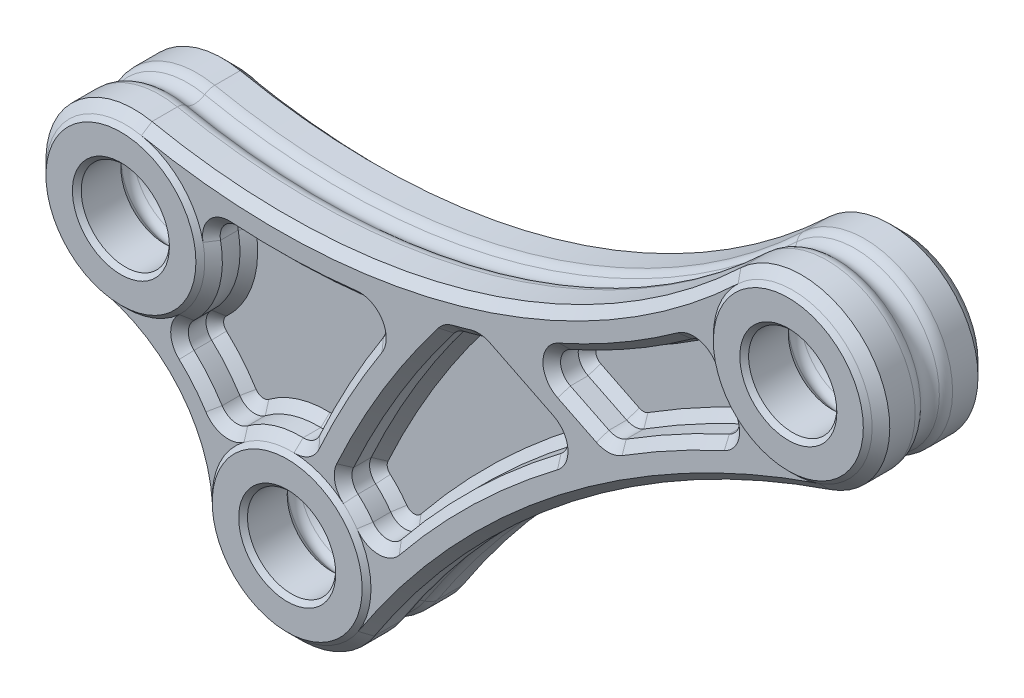
SolidWorks part; units mm, degrees
material "7075-T6，板材(SS)"
ref_plane "前视基准面" through (0, 0, 0) normal (0, 0, 1) x (1, 0, 0)
ref_plane "上视基准面" through (0, 0, 0) normal (0, 1, 0) x (1, 0, 0)
ref_plane "右视基准面" through (0, 0, 0) normal (1, 0, 0) x (0, 0, -1)
sketch "Sketch1" plane through (0, 0, 0) normal (0, 0, 1) x (1, 0, 0)
  line L0 (122.9511, -18.8201) -> (93.1268, -73.5554)
  line L1 (93.1268, -73.5554) -> (122.7846, -133.2618)
  line L2 (122.7846, -133.2618) -> (122.9511, -18.8201)
  line L3 (0, 0) -> (71.4018, 54.7885)
  line L4 (71.4018, 54.7885) -> (-333.3333, 54.7885)
  line L5 (-333.3333, 54.7885) -> (0, 0)
  line L6 (0, 0) -> (-333.3333, 54.7885)
  line L7 (-333.3333, 54.7885) -> (-333.3333, 0)
  line L8 (-333.3333, 0) -> (0, 0)
  line L9 (71.4018, 54.7885) -> (122.9511, -18.8201)
  line L10 (122.9511, -18.8201) -> (94.2741, 2.9429)
  line L11 (94.2741, 2.9429) -> (71.4018, 54.7885)
  line L12 (71.4018, 54.7885) -> (94.2741, 2.9429)
  line L13 (94.2741, 2.9429) -> (71.4018, 54.7885)
  line L14 (94.2741, 2.9429) -> (18.6205, -18.6205)
  line L15 (18.6205, -18.6205) -> (37.467, -41.2946)
  line L16 (37.467, -41.2946) -> (94.2741, 2.9429)
  line L17 (94.2741, 2.9429) -> (37.467, -41.2946)
  line L18 (37.467, -41.2946) -> (94.2741, 2.9429)
  line L19 (184.818, -172.2512) -> (184.6311, -172.3314)
  line L20 (184.6311, -172.3314) -> (184.444, -172.4113)
  line L21 (184.444, -172.4113) -> (184.2569, -172.4911)
  line L22 (184.2569, -172.4911) -> (184.0696, -172.5706)
  line L23 (184.0696, -172.5706) -> (183.8823, -172.6498)
  line L24 (183.8823, -172.6498) -> (183.6948, -172.7288)
  line L25 (183.6948, -172.7288) -> (183.5072, -172.8076)
  line L26 (183.5072, -172.8076) -> (183.3195, -172.8862)
  line L27 (183.3195, -172.8862) -> (183.1318, -172.9645)
  line L28 (183.1318, -172.9645) -> (182.9439, -173.0426)
  line L29 (182.9439, -173.0426) -> (182.7559, -173.1204)
  line L30 (182.7559, -173.1204) -> (182.5679, -173.198)
  line L31 (182.5679, -173.198) -> (182.3797, -173.2753)
  line L32 (182.3797, -173.2753) -> (182.1914, -173.3524)
  line L33 (182.1914, -173.3524) -> (182.003, -173.4293)
  line L34 (182.003, -173.4293) -> (181.8146, -173.5059)
  line L35 (181.8146, -173.5059) -> (181.626, -173.5823)
  line L36 (181.626, -173.5823) -> (181.4374, -173.6584)
  line L37 (181.4374, -173.6584) -> (181.2486, -173.7343)
  line L38 (181.2486, -173.7343) -> (181.0598, -173.8099)
  line L39 (181.0598, -173.8099) -> (180.8709, -173.8853)
  line L40 (180.8709, -173.8853) -> (180.6819, -173.9604)
  line L41 (180.6819, -173.9604) -> (180.4928, -174.0353)
  line L42 (180.4928, -174.0353) -> (180.3036, -174.11)
  line L43 (180.3036, -174.11) -> (180.1143, -174.1843)
  line L44 (180.1143, -174.1843) -> (179.9249, -174.2585)
  line L45 (179.9249, -174.2585) -> (179.7355, -174.3324)
  line L46 (179.7355, -174.3324) -> (179.546, -174.406)
  line L47 (179.546, -174.406) -> (179.3564, -174.4794)
  line L48 (179.3564, -174.4794) -> (179.1667, -174.5525)
  line L49 (179.1667, -174.5525) -> (178.9769, -174.6254)
  line L50 (178.9769, -174.6254) -> (178.7871, -174.698)
  line L51 (178.7871, -174.698) -> (178.5972, -174.7704)
  line L52 (178.5972, -174.7704) -> (178.4072, -174.8425)
  line L53 (178.4072, -174.8425) -> (178.2172, -174.9143)
  line L54 (178.2172, -174.9143) -> (178.027, -174.9859)
  line L55 (178.027, -174.9859) -> (177.8368, -175.0573)
  line L56 (177.8368, -175.0573) -> (177.6466, -175.1283)
  line L57 (177.6466, -175.1283) -> (177.4563, -175.1992)
  line L58 (177.4563, -175.1992) -> (177.2659, -175.2697)
  line L59 (177.2659, -175.2697) -> (177.0754, -175.34)
  line L60 (177.0754, -175.34) -> (176.8849, -175.41)
  line L61 (176.8849, -175.41) -> (176.6943, -175.4798)
  line L62 (176.6943, -175.4798) -> (176.5037, -175.5493)
  line L63 (176.5037, -175.5493) -> (176.313, -175.6186)
  line L64 (176.313, -175.6186) -> (176.1223, -175.6875)
  line L65 (176.1223, -175.6875) -> (175.9315, -175.7562)
  line L66 (175.9315, -175.7562) -> (175.7407, -175.8247)
  line L67 (175.7407, -175.8247) -> (175.5498, -175.8928)
  line L68 (175.5498, -175.8928) -> (175.3588, -175.9608)
  line L69 (175.3588, -175.9608) -> (175.1679, -176.0284)
  line L70 (175.1679, -176.0284) -> (174.9768, -176.0958)
  line L71 (174.9768, -176.0958) -> (174.7858, -176.1629)
  line L72 (174.7858, -176.1629) -> (174.5947, -176.2297)
  line L73 (174.5947, -176.2297) -> (174.4036, -176.2962)
  line L74 (174.4036, -176.2962) -> (174.2124, -176.3625)
  line L75 (174.2124, -176.3625) -> (174.0212, -176.4285)
  line L76 (174.0212, -176.4285) -> (173.8299, -176.4943)
  line L77 (173.8299, -176.4943) -> (173.6387, -176.5597)
  line L78 (173.6387, -176.5597) -> (173.4474, -176.6249)
  line L79 (173.4474, -176.6249) -> (173.2561, -176.6898)
  line L80 (173.2561, -176.6898) -> (173.0648, -176.7545)
  line L81 (173.0648, -176.7545) -> (172.8734, -176.8188)
  line L82 (172.8734, -176.8188) -> (172.682, -176.8829)
  line L83 (172.682, -176.8829) -> (172.4906, -176.9467)
  line L84 (172.4906, -176.9467) -> (172.2992, -177.0102)
  line L85 (172.2992, -177.0102) -> (172.1078, -177.0735)
  line L86 (172.1078, -177.0735) -> (171.9164, -177.1365)
  line L87 (171.9164, -177.1365) -> (171.725, -177.1991)
  line L88 (171.725, -177.1991) -> (171.5335, -177.2616)
  line L89 (171.5335, -177.2616) -> (171.3421, -177.3237)
  line L90 (171.3421, -177.3237) -> (171.1507, -177.3855)
  line L91 (171.1507, -177.3855) -> (170.9592, -177.4471)
  line L92 (170.9592, -177.4471) -> (170.7678, -177.5083)
  line L93 (170.7678, -177.5083) -> (170.5764, -177.5693)
  line L94 (170.5764, -177.5693) -> (170.385, -177.63)
  line L95 (170.385, -177.63) -> (170.1936, -177.6905)
  line L96 (170.1936, -177.6905) -> (170.0022, -177.7506)
  line L97 (170.0022, -177.7506) -> (169.8108, -177.8104)
  line L98 (169.8108, -177.8104) -> (169.6194, -177.87)
  line L99 (169.6194, -177.87) -> (169.4281, -177.9293)
  line L100 (169.4281, -177.9293) -> (169.2368, -177.9883)
  line L101 (169.2368, -177.9883) -> (169.0455, -178.047)
  line L102 (169.0455, -178.047) -> (168.8543, -178.1054)
  line L103 (168.8543, -178.1054) -> (168.6631, -178.1635)
  line L104 (168.6631, -178.1635) -> (168.4719, -178.2213)
  line L105 (168.4719, -178.2213) -> (168.2807, -178.2789)
  line L106 (168.2807, -178.2789) -> (168.0896, -178.3361)
  line L107 (168.0896, -178.3361) -> (167.8985, -178.3931)
  line L108 (167.8985, -178.3931) -> (167.7075, -178.4497)
  line L109 (167.7075, -178.4497) -> (167.5165, -178.5061)
  line L110 (167.5165, -178.5061) -> (167.3256, -178.5622)
  line L111 (167.3256, -178.5622) -> (167.1347, -178.618)
  line L112 (167.1347, -178.618) -> (166.9439, -178.6735)
  line L113 (166.9439, -178.6735) -> (166.7531, -178.7287)
  line L114 (166.7531, -178.7287) -> (166.5624, -178.7836)
  line L115 (166.5624, -178.7836) -> (166.3718, -178.8382)
  line L116 (166.3718, -178.8382) -> (166.1812, -178.8925)
  line L117 (166.1812, -178.8925) -> (165.9907, -178.9465)
  line L118 (165.9907, -178.9465) -> (165.8003, -179.0002)
  line L119 (165.8003, -179.0002) -> (165.6099, -179.0537)
  line L120 (165.6099, -179.0537) -> (165.4196, -179.1068)
  line L121 (165.4196, -179.1068) -> (165.2294, -179.1596)
  line L122 (165.2294, -179.1596) -> (165.0393, -179.2122)
  line L123 (165.0393, -179.2122) -> (164.8492, -179.2644)
  line L124 (164.8492, -179.2644) -> (164.6593, -179.3164)
  line L125 (164.6593, -179.3164) -> (164.4694, -179.368)
  line L126 (164.4694, -179.368) -> (164.2796, -179.4193)
  line L127 (164.2796, -179.4193) -> (164.09, -179.4704)
  line L128 (164.09, -179.4704) -> (163.9004, -179.5211)
  line L129 (163.9004, -179.5211) -> (163.7109, -179.5716)
  line L130 (163.7109, -179.5716) -> (163.5215, -179.6218)
  line L131 (163.5215, -179.6218) -> (163.3323, -179.6716)
  line L132 (163.3323, -179.6716) -> (163.1431, -179.7212)
  line L133 (163.1431, -179.7212) -> (162.9541, -179.7704)
  line L134 (162.9541, -179.7704) -> (162.7651, -179.8194)
  line L135 (162.7651, -179.8194) -> (162.5763, -179.868)
  line L136 (162.5763, -179.868) -> (162.3877, -179.9164)
  line L137 (162.3877, -179.9164) -> (162.1991, -179.9644)
  line L138 (162.1991, -179.9644) -> (162.0107, -180.0122)
  line L139 (162.0107, -180.0122) -> (161.8224, -180.0596)
  line L140 (161.8224, -180.0596) -> (161.6342, -180.1068)
  line L141 (161.6342, -180.1068) -> (161.4462, -180.1536)
  line L142 (161.4462, -180.1536) -> (161.2583, -180.2002)
  line L143 (161.2583, -180.2002) -> (161.0705, -180.2464)
  line L144 (161.0705, -180.2464) -> (160.8829, -180.2924)
  line L145 (160.8829, -180.2924) -> (160.6955, -180.338)
  line L146 (160.6955, -180.338) -> (160.5082, -180.3834)
  line L147 (160.5082, -180.3834) -> (160.321, -180.4284)
  line L148 (160.321, -180.4284) -> (160.134, -180.4732)
  line L149 (160.134, -180.4732) -> (159.9472, -180.5176)
  line L150 (159.9472, -180.5176) -> (159.7605, -180.5617)
  line L151 (159.7605, -180.5617) -> (159.574, -180.6056)
  line L152 (159.574, -180.6056) -> (159.3877, -180.6491)
  line L153 (159.3877, -180.6491) -> (159.2015, -180.6924)
  line L154 (159.2015, -180.6924) -> (159.0156, -180.7353)
  line L155 (159.0156, -180.7353) -> (158.8298, -180.7779)
  line L156 (158.8298, -180.7779) -> (158.6441, -180.8203)
  line L157 (158.6441, -180.8203) -> (158.4587, -180.8623)
  line L158 (158.4587, -180.8623) -> (158.2735, -180.904)
  line L159 (158.2735, -180.904) -> (158.0884, -180.9455)
  line L160 (158.0884, -180.9455) -> (157.9035, -180.9866)
  line L161 (157.9035, -180.9866) -> (157.7189, -181.0274)
  line L162 (157.7189, -181.0274) -> (157.5344, -181.068)
  line L163 (157.5344, -181.068) -> (157.3502, -181.1082)
  line L164 (157.3502, -181.1082) -> (157.1661, -181.1481)
  line L165 (157.1661, -181.1481) -> (156.9823, -181.1878)
  line L166 (156.9823, -181.1878) -> (156.7986, -181.2271)
  line L167 (156.7986, -181.2271) -> (156.6152, -181.2662)
  line L168 (156.6152, -181.2662) -> (156.432, -181.3049)
  line L169 (156.432, -181.3049) -> (156.249, -181.3433)
  line L170 (156.249, -181.3433) -> (156.0663, -181.3815)
  line L171 (156.0663, -181.3815) -> (155.8838, -181.4193)
  line L172 (155.8838, -181.4193) -> (155.7015, -181.4569)
  line L173 (155.7015, -181.4569) -> (155.5194, -181.4941)
  line L174 (155.5194, -181.4941) -> (155.3376, -181.5311)
  line L175 (155.3376, -181.5311) -> (155.156, -181.5678)
  line L176 (155.156, -181.5678) -> (154.9747, -181.6041)
  line L177 (154.9747, -181.6041) -> (154.7936, -181.6402)
  line L178 (154.7936, -181.6402) -> (154.6127, -181.676)
  line L179 (154.6127, -181.676) -> (154.4322, -181.7114)
  line L180 (154.4322, -181.7114) -> (154.2518, -181.7466)
  line L181 (154.2518, -181.7466) -> (154.0718, -181.7815)
  line L182 (154.0718, -181.7815) -> (153.892, -181.8161)
  line L183 (153.892, -181.8161) -> (153.7124, -181.8504)
  line L184 (153.7124, -181.8504) -> (153.5331, -181.8844)
  line L185 (153.5331, -181.8844) -> (153.3541, -181.9181)
  line L186 (153.3541, -181.9181) -> (153.1754, -181.9516)
  line L187 (153.1754, -181.9516) -> (152.9969, -181.9847)
  line L188 (152.9969, -181.9847) -> (152.8188, -182.0176)
  line L189 (152.8188, -182.0176) -> (152.6409, -182.0501)
  line L190 (152.6409, -182.0501) -> (152.4633, -182.0824)
  line L191 (152.4633, -182.0824) -> (152.286, -182.1144)
  line L192 (152.286, -182.1144) -> (152.109, -182.1461)
  line L193 (152.109, -182.1461) -> (151.9322, -182.1775)
  line L194 (151.9322, -182.1775) -> (151.7558, -182.2086)
  line L195 (151.7558, -182.2086) -> (151.5797, -182.2394)
  line L196 (151.5797, -182.2394) -> (151.4039, -182.27)
  line L197 (151.4039, -182.27) -> (151.2284, -182.3002)
  line L198 (151.2284, -182.3002) -> (151.0532, -182.3302)
  line L199 (151.0532, -182.3302) -> (150.8783, -182.3599)
  line L200 (150.8783, -182.3599) -> (150.7037, -182.3893)
  line L201 (150.7037, -182.3893) -> (150.5295, -182.4184)
  line L202 (150.5295, -182.4184) -> (150.3555, -182.4473)
  line L203 (150.3555, -182.4473) -> (150.1819, -182.4758)
  line L204 (150.1819, -182.4758) -> (150.0087, -182.5041)
  line L205 (150.0087, -182.5041) -> (149.8357, -182.5321)
  line L206 (149.8357, -182.5321) -> (149.6631, -182.5598)
  line L207 (149.6631, -182.5598) -> (149.4908, -182.5873)
  line L208 (149.4908, -182.5873) -> (149.3189, -182.6145)
  line L209 (149.3189, -182.6145) -> (149.1473, -182.6413)
  line L210 (149.1473, -182.6413) -> (148.9761, -182.668)
  line L211 (148.9761, -182.668) -> (148.8052, -182.6943)
  line L212 (148.8052, -182.6943) -> (148.6347, -182.7204)
  line L213 (148.6347, -182.7204) -> (148.4645, -182.7462)
  line L214 (148.4645, -182.7462) -> (148.2946, -182.7717)
  line L215 (148.2946, -182.7717) -> (148.1252, -182.797)
  line L216 (148.1252, -182.797) -> (147.9561, -182.8219)
  line L217 (147.9561, -182.8219) -> (147.7873, -182.8467)
  line L218 (147.7873, -182.8467) -> (147.619, -182.8711)
  line L219 (147.619, -182.8711) -> (147.451, -182.8953)
  line L220 (147.451, -182.8953) -> (147.2833, -182.9192)
  line L221 (147.2833, -182.9192) -> (147.1161, -182.9429)
  line L222 (147.1161, -182.9429) -> (146.9492, -182.9662)
  line L223 (146.9492, -182.9662) -> (146.7827, -182.9894)
  line L224 (146.7827, -182.9894) -> (146.6166, -183.0122)
  line L225 (146.6166, -183.0122) -> (146.4509, -183.0348)
  line L226 (146.4509, -183.0348) -> (146.2856, -183.0571)
  line L227 (146.2856, -183.0571) -> (146.1206, -183.0792)
  line L228 (146.1206, -183.0792) -> (145.9561, -183.101)
  line L229 (145.9561, -183.101) -> (145.7919, -183.1226)
  line L230 (145.7919, -183.1226) -> (145.6282, -183.1439)
  line L231 (145.6282, -183.1439) -> (145.4649, -183.165)
  line L232 (145.4649, -183.165) -> (145.3019, -183.1858)
  line L233 (145.3019, -183.1858) -> (145.1394, -183.2063)
  line L234 (145.1394, -183.2063) -> (144.9773, -183.2266)
  line L235 (144.9773, -183.2266) -> (144.8156, -183.2466)
  line L236 (144.8156, -183.2466) -> (144.6543, -183.2664)
  line L237 (144.6543, -183.2664) -> (144.4934, -183.286)
  line L238 (144.4934, -183.286) -> (144.3329, -183.3053)
  line L239 (144.3329, -183.3053) -> (144.1729, -183.3243)
  line L240 (144.1729, -183.3243) -> (144.0133, -183.3431)
  line L241 (144.0133, -183.3431) -> (143.8541, -183.3617)
  line L242 (143.8541, -183.3617) -> (143.6953, -183.38)
  line L243 (143.6953, -183.38) -> (143.537, -183.3981)
  line L244 (143.537, -183.3981) -> (143.3791, -183.4159)
  line L245 (143.3791, -183.4159) -> (143.2217, -183.4335)
  line L246 (143.2217, -183.4335) -> (143.0646, -183.4508)
  line L247 (143.0646, -183.4508) -> (142.908, -183.468)
  line L248 (142.908, -183.468) -> (142.7519, -183.4849)
  line L249 (142.7519, -183.4849) -> (142.5962, -183.5015)
  line L250 (142.5962, -183.5015) -> (142.4409, -183.5179)
  line L251 (142.4409, -183.5179) -> (142.2861, -183.5341)
  line L252 (142.2861, -183.5341) -> (142.1318, -183.5501)
  line L253 (142.1318, -183.5501) -> (141.9778, -183.5658)
  line L254 (141.9778, -183.5658) -> (141.8244, -183.5813)
  line L255 (141.8244, -183.5813) -> (141.6714, -183.5966)
  line L256 (141.6714, -183.5966) -> (141.5188, -183.6116)
  line L257 (141.5188, -183.6116) -> (141.3667, -183.6265)
  line L258 (141.3667, -183.6265) -> (141.2151, -183.6411)
  line L259 (141.2151, -183.6411) -> (141.0639, -183.6554)
  line L260 (141.0639, -183.6554) -> (140.9132, -183.6696)
  line L261 (140.9132, -183.6696) -> (140.7629, -183.6836)
  line L262 (140.7629, -183.6836) -> (140.6132, -183.6973)
  line L263 (140.6132, -183.6973) -> (140.4638, -183.7108)
  line L264 (140.4638, -183.7108) -> (140.315, -183.7241)
  line L265 (140.315, -183.7241) -> (140.1666, -183.7372)
  line L266 (140.1666, -183.7372) -> (140.0187, -183.7501)
  line L267 (140.0187, -183.7501) -> (139.8713, -183.7627)
  line L268 (139.8713, -183.7627) -> (139.7243, -183.7752)
  line L269 (139.7243, -183.7752) -> (139.5778, -183.7874)
  line L270 (139.5778, -183.7874) -> (139.4318, -183.7995)
  line L271 (139.4318, -183.7995) -> (139.2863, -183.8113)
  line L272 (139.2863, -183.8113) -> (139.1412, -183.823)
  line L273 (139.1412, -183.823) -> (138.9966, -183.8344)
  line L274 (138.9966, -183.8344) -> (138.8525, -183.8456)
  line L275 (138.8525, -183.8456) -> (138.7089, -183.8567)
  line L276 (138.7089, -183.8567) -> (138.5658, -183.8675)
  line L277 (138.5658, -183.8675) -> (138.4231, -183.8781)
  line L278 (138.4231, -183.8781) -> (138.2809, -183.8886)
  line L279 (138.2809, -183.8886) -> (138.1393, -183.8988)
  line L280 (138.1393, -183.8988) -> (137.998, -183.9089)
  line L281 (137.998, -183.9089) -> (137.8573, -183.9188)
  line L282 (137.8573, -183.9188) -> (137.7171, -183.9285)
  line L283 (137.7171, -183.9285) -> (137.5773, -183.938)
  line L284 (137.5773, -183.938) -> (137.4381, -183.9473)
  line L285 (137.4381, -183.9473) -> (137.2993, -183.9564)
  line L286 (137.2993, -183.9564) -> (137.161, -183.9654)
  line L287 (137.161, -183.9654) -> (137.0232, -183.9741)
  line L288 (137.0232, -183.9741) -> (136.8859, -183.9827)
  line L289 (136.8859, -183.9827) -> (136.7491, -183.9911)
  line L290 (136.7491, -183.9911) -> (136.6127, -183.9994)
  line L291 (136.6127, -183.9994) -> (136.4769, -184.0074)
  line L292 (136.4769, -184.0074) -> (136.3415, -184.0153)
  line L293 (136.3415, -184.0153) -> (136.2066, -184.023)
  line L294 (136.2066, -184.023) -> (136.0722, -184.0306)
  line L295 (136.0722, -184.0306) -> (135.9383, -184.0379)
  line L296 (135.9383, -184.0379) -> (135.8049, -184.0451)
  line L297 (135.8049, -184.0451) -> (135.672, -184.0522)
  line L298 (135.672, -184.0522) -> (135.5395, -184.0591)
  line L299 (135.5395, -184.0591) -> (135.4075, -184.0658)
  line L300 (135.4075, -184.0658) -> (135.276, -184.0723)
  line L301 (135.276, -184.0723) -> (135.145, -184.0787)
  line L302 (135.145, -184.0787) -> (135.0145, -184.0849)
  line L303 (135.0145, -184.0849) -> (134.8845, -184.091)
  line L304 (134.8845, -184.091) -> (134.7549, -184.0969)
  line L305 (134.7549, -184.0969) -> (134.6258, -184.1027)
  line L306 (134.6258, -184.1027) -> (134.4972, -184.1083)
  line L307 (134.4972, -184.1083) -> (134.3691, -184.1137)
  line L308 (134.3691, -184.1137) -> (134.2414, -184.119)
  line L309 (134.2414, -184.119) -> (134.1142, -184.1242)
  line L310 (134.1142, -184.1242) -> (133.9875, -184.1292)
  line L311 (133.9875, -184.1292) -> (133.8613, -184.1341)
  line L312 (133.8613, -184.1341) -> (133.7355, -184.1388)
  line L313 (133.7355, -184.1388) -> (133.6102, -184.1434)
  line L314 (133.6102, -184.1434) -> (133.4853, -184.1478)
  line L315 (133.4853, -184.1478) -> (133.3609, -184.1521)
  line L316 (133.3609, -184.1521) -> (133.237, -184.1563)
  line L317 (133.237, -184.1563) -> (133.1135, -184.1603)
  line L318 (133.1135, -184.1603) -> (132.9905, -184.1642)
  line L319 (132.9905, -184.1642) -> (132.8679, -184.1679)
  line L320 (132.8679, -184.1679) -> (132.7458, -184.1715)
  line L321 (132.7458, -184.1715) -> (132.6242, -184.175)
  line L322 (132.6242, -184.175) -> (132.5029, -184.1784)
  line L323 (132.5029, -184.1784) -> (132.3821, -184.1816)
  line L324 (132.3821, -184.1816) -> (132.2618, -184.1847)
  line L325 (132.2618, -184.1847) -> (132.1419, -184.1877)
  line L326 (132.1419, -184.1877) -> (132.0224, -184.1905)
  line L327 (132.0224, -184.1905) -> (131.9033, -184.1933)
  line L328 (131.9033, -184.1933) -> (131.7847, -184.1959)
  line L329 (131.7847, -184.1959) -> (131.6665, -184.1983)
  line L330 (131.6665, -184.1983) -> (131.5487, -184.2007)
  line L331 (131.5487, -184.2007) -> (131.4313, -184.2029)
  line L332 (131.4313, -184.2029) -> (131.3144, -184.2051)
  line L333 (131.3144, -184.2051) -> (131.1978, -184.2071)
  line L334 (131.1978, -184.2071) -> (131.0816, -184.209)
  line L335 (131.0816, -184.209) -> (130.9658, -184.2107)
  line L336 (130.9658, -184.2107) -> (130.8505, -184.2124)
  line L337 (130.8505, -184.2124) -> (130.7355, -184.214)
  line L338 (130.7355, -184.214) -> (130.6209, -184.2154)
  line L339 (130.6209, -184.2154) -> (130.5066, -184.2168)
  line L340 (130.5066, -184.2168) -> (130.3927, -184.218)
  line L341 (130.3927, -184.218) -> (130.2792, -184.2191)
  line L342 (130.2792, -184.2191) -> (130.1661, -184.2201)
  line L343 (130.1661, -184.2201) -> (130.0533, -184.221)
  line L344 (130.0533, -184.221) -> (129.9409, -184.2219)
  line L345 (129.9409, -184.2219) -> (129.8288, -184.2226)
  line L346 (129.8288, -184.2226) -> (129.717, -184.2232)
  line L347 (129.717, -184.2232) -> (129.6056, -184.2237)
  line L348 (129.6056, -184.2237) -> (129.4945, -184.2241)
  line L349 (129.4945, -184.2241) -> (129.3837, -184.2244)
  line L350 (129.3837, -184.2244) -> (129.2732, -184.2246)
  line L351 (129.2732, -184.2246) -> (129.163, -184.2247)
  line L352 (129.163, -184.2247) -> (129.0531, -184.2248)
  line L353 (129.0531, -184.2248) -> (128.9435, -184.2247)
  line L354 (128.9435, -184.2247) -> (128.8342, -184.2245)
  line L355 (128.8342, -184.2245) -> (128.7251, -184.2243)
  line L356 (128.7251, -184.2243) -> (128.6163, -184.2239)
  line L357 (128.6163, -184.2239) -> (128.5078, -184.2235)
  line L358 (128.5078, -184.2235) -> (128.3995, -184.223)
  line L359 (128.3995, -184.223) -> (128.2915, -184.2223)
  line L360 (128.2915, -184.2223) -> (128.1836, -184.2216)
  line L361 (128.1836, -184.2216) -> (128.076, -184.2208)
  line L362 (128.076, -184.2208) -> (127.9686, -184.22)
  line L363 (127.9686, -184.22) -> (127.8615, -184.219)
  line L364 (127.8615, -184.219) -> (127.7544, -184.2179)
  line L365 (127.7544, -184.2179) -> (127.6476, -184.2168)
  line L366 (127.6476, -184.2168) -> (127.541, -184.2156)
  line L367 (127.541, -184.2156) -> (127.4345, -184.2143)
  line L368 (127.4345, -184.2143) -> (127.3281, -184.2129)
  line L369 (127.3281, -184.2129) -> (127.2219, -184.2114)
  line L370 (127.2219, -184.2114) -> (127.1158, -184.2098)
  line L371 (127.1158, -184.2098) -> (127.0099, -184.2082)
  line L372 (127.0099, -184.2082) -> (126.904, -184.2065)
  line L373 (126.904, -184.2065) -> (126.7982, -184.2047)
  line L374 (126.7982, -184.2047) -> (126.6925, -184.2028)
  line L375 (126.6925, -184.2028) -> (126.5868, -184.2008)
  line L376 (126.5868, -184.2008) -> (126.4813, -184.1988)
  line L377 (126.4813, -184.1988) -> (126.3757, -184.1966)
  line L378 (126.3757, -184.1966) -> (126.2702, -184.1944)
  line L379 (126.2702, -184.1944) -> (126.1646, -184.1922)
  line L380 (126.1646, -184.1922) -> (126.0591, -184.1898)
  line L381 (126.0591, -184.1898) -> (125.9535, -184.1873)
  line L382 (125.9535, -184.1873) -> (125.848, -184.1848)
  line L383 (125.848, -184.1848) -> (125.7423, -184.1822)
  line L384 (125.7423, -184.1822) -> (125.6366, -184.1795)
  line L385 (125.6366, -184.1795) -> (125.5308, -184.1767)
  line L386 (125.5308, -184.1767) -> (125.4249, -184.1739)
  line L387 (125.4249, -184.1739) -> (125.3189, -184.171)
  line L388 (125.3189, -184.171) -> (125.2128, -184.168)
  line L389 (125.2128, -184.168) -> (125.1065, -184.1649)
  line L390 (125.1065, -184.1649) -> (125, -184.1617)
  line L391 (125, -184.1617) -> (124.8933, -184.1584)
  line L392 (124.8933, -184.1584) -> (124.7865, -184.1551)
  line L393 (124.7865, -184.1551) -> (124.6794, -184.1517)
  line L394 (124.6794, -184.1517) -> (124.572, -184.1482)
  line L395 (124.572, -184.1482) -> (124.4644, -184.1446)
  line L396 (124.4644, -184.1446) -> (124.3565, -184.1409)
  line L397 (124.3565, -184.1409) -> (124.2483, -184.1372)
  line L398 (124.2483, -184.1372) -> (124.1397, -184.1333)
  line L399 (124.1397, -184.1333) -> (124.0308, -184.1294)
  line L400 (124.0308, -184.1294) -> (123.9215, -184.1254)
  line L401 (123.9215, -184.1254) -> (123.8118, -184.1213)
  line L402 (123.8118, -184.1213) -> (123.7017, -184.1171)
  line L403 (123.7017, -184.1171) -> (123.5911, -184.1128)
  line L404 (123.5911, -184.1128) -> (123.4801, -184.1084)
  line L405 (123.4801, -184.1084) -> (123.3685, -184.1039)
  line L406 (123.3685, -184.1039) -> (123.2564, -184.0994)
  line L407 (123.2564, -184.0994) -> (123.1438, -184.0947)
  line L408 (123.1438, -184.0947) -> (123.0306, -184.0899)
  line L409 (123.0306, -184.0899) -> (122.9167, -184.0851)
  line L410 (122.9167, -184.0851) -> (122.8022, -184.0801)
  line L411 (122.8022, -184.0801) -> (122.6871, -184.075)
  line L412 (122.6871, -184.075) -> (122.5712, -184.0699)
  line L413 (122.5712, -184.0699) -> (122.4547, -184.0646)
  line L414 (122.4547, -184.0646) -> (122.3373, -184.0592)
  line L415 (122.3373, -184.0592) -> (122.2192, -184.0537)
  line L416 (122.2192, -184.0537) -> (122.1002, -184.0481)
  line L417 (122.1002, -184.0481) -> (121.9804, -184.0424)
  line L418 (121.9804, -184.0424) -> (121.8596, -184.0366)
  line L419 (121.8596, -184.0366) -> (121.7379, -184.0306)
  line L420 (121.7379, -184.0306) -> (121.6153, -184.0245)
  line L421 (121.6153, -184.0245) -> (121.4916, -184.0183)
  line L422 (121.4916, -184.0183) -> (121.3669, -184.012)
  line L423 (121.3669, -184.012) -> (121.2411, -184.0055)
  line L424 (121.2411, -184.0055) -> (121.1142, -183.9989)
  line L425 (121.1142, -183.9989) -> (120.9861, -183.9922)
  line L426 (120.9861, -183.9922) -> (120.8568, -183.9854)
  line L427 (120.8568, -183.9854) -> (120.7262, -183.9784)
  line L428 (120.7262, -183.9784) -> (120.5944, -183.9712)
  line L429 (120.5944, -183.9712) -> (120.4612, -183.9639)
  line L430 (120.4612, -183.9639) -> (120.3266, -183.9565)
  line L431 (120.3266, -183.9565) -> (120.1905, -183.9488)
  line L432 (120.1905, -183.9488) -> (120.053, -183.9411)
  line L433 (120.053, -183.9411) -> (119.9139, -183.9332)
  line L434 (119.9139, -183.9332) -> (119.7732, -183.9251)
  line L435 (119.7732, -183.9251) -> (119.6309, -183.9168)
  line L436 (119.6309, -183.9168) -> (119.4869, -183.9083)
  line L437 (119.4869, -183.9083) -> (119.3411, -183.8997)
  line L438 (119.3411, -183.8997) -> (119.1935, -183.8909)
  line L439 (119.1935, -183.8909) -> (119.044, -183.8819)
  line L440 (119.044, -183.8819) -> (118.8926, -183.8727)
  line L441 (118.8926, -183.8727) -> (118.7392, -183.8633)
  line L442 (118.7392, -183.8633) -> (118.5837, -183.8537)
  line L443 (118.5837, -183.8537) -> (118.4262, -183.8439)
  line L444 (118.4262, -183.8439) -> (118.2664, -183.8338)
  line L445 (118.2664, -183.8338) -> (118.1043, -183.8236)
  line L446 (118.1043, -183.8236) -> (117.9399, -183.8131)
  line L447 (117.9399, -183.8131) -> (117.7732, -183.8023)
  line L448 (117.7732, -183.8023) -> (117.6039, -183.7914)
  line L449 (117.6039, -183.7914) -> (117.4321, -183.7801)
  line L450 (117.4321, -183.7801) -> (117.2576, -183.7687)
  line L451 (117.2576, -183.7687) -> (117.0804, -183.7569)
  line L452 (117.0804, -183.7569) -> (116.9004, -183.7449)
  line L453 (116.9004, -183.7449) -> (116.7175, -183.7326)
  line L454 (116.7175, -183.7326) -> (116.5317, -183.72)
  line L455 (116.5317, -183.72) -> (116.3428, -183.7072)
  line L456 (116.3428, -183.7072) -> (116.1507, -183.694)
  line L457 (116.1507, -183.694) -> (115.9553, -183.6805)
  line L458 (115.9553, -183.6805) -> (115.7566, -183.6667)
  line L459 (115.7566, -183.6667) -> (115.5545, -183.6525)
  line L460 (115.5545, -183.6525) -> (115.3487, -183.638)
  line L461 (115.3487, -183.638) -> (115.1393, -183.6232)
  line L462 (115.1393, -183.6232) -> (114.9261, -183.608)
  line L463 (114.9261, -183.608) -> (114.709, -183.5924)
  line L464 (114.709, -183.5924) -> (114.4879, -183.5764)
  line L465 (114.4879, -183.5764) -> (114.2627, -183.5601)
  line L466 (114.2627, -183.5601) -> (114.0331, -183.5433)
  line L467 (114.0331, -183.5433) -> (113.7992, -183.5261)
  line L468 (113.7992, -183.5261) -> (113.5608, -183.5085)
  line L469 (113.5608, -183.5085) -> (113.3176, -183.4905)
  line L470 (113.3176, -183.4905) -> (113.0697, -183.4719)
  line L471 (113.0697, -183.4719) -> (112.8168, -183.4529)
  line L472 (112.8168, -183.4529) -> (112.5588, -183.4335)
  line L473 (112.5588, -183.4335) -> (112.2955, -183.4135)
  line L474 (112.2955, -183.4135) -> (112.0268, -183.393)
  line L475 (112.0268, -183.393) -> (111.7525, -183.372)
  line L476 (111.7525, -183.372) -> (111.4724, -183.3504)
  line L477 (111.4724, -183.3504) -> (111.1863, -183.3282)
  line L478 (111.1863, -183.3282) -> (110.8942, -183.3055)
  line L479 (110.8942, -183.3055) -> (110.5956, -183.2821)
  line L480 (110.5956, -183.2821) -> (110.2906, -183.2582)
  line L481 (110.2906, -183.2582) -> (109.9788, -183.2335)
  line L482 (109.9788, -183.2335) -> (109.6601, -183.2083)
  line L483 (109.6601, -183.2083) -> (109.3343, -183.1823)
  line L484 (109.3343, -183.1823) -> (109.001, -183.1556)
  line L485 (109.001, -183.1556) -> (108.6601, -183.1282)
  line L486 (108.6601, -183.1282) -> (108.3113, -183.1001)
  line L487 (108.3113, -183.1001) -> (107.9544, -183.0711)
  line L488 (107.9544, -183.0711) -> (107.5891, -183.0414)
  line L489 (107.5891, -183.0414) -> (107.2151, -183.0108)
  line L490 (107.2151, -183.0108) -> (106.8322, -182.9794)
  line L491 (106.8322, -182.9794) -> (106.4401, -182.9471)
  line L492 (106.4401, -182.9471) -> (106.0384, -182.9138)
  line L493 (106.0384, -182.9138) -> (105.6268, -182.8796)
  line L494 (105.6268, -182.8796) -> (105.2051, -182.8445)
  line L495 (105.2051, -182.8445) -> (104.7728, -182.8083)
  line L496 (104.7728, -182.8083) -> (104.3296, -182.7711)
  line L497 (104.3296, -182.7711) -> (103.8751, -182.7327)
  line L498 (103.8751, -182.7327) -> (103.409, -182.6933)
  line L499 (103.409, -182.6933) -> (102.9308, -182.6527)
  line L500 (102.9308, -182.6527) -> (102.4402, -182.6108)
  line L501 (102.4402, -182.6108) -> (101.9366, -182.5678)
  line L502 (101.9366, -182.5678) -> (101.4196, -182.5234)
  line L503 (101.4196, -182.5234) -> (100.8889, -182.4777)
  line L504 (100.8889, -182.4777) -> (100.3437, -182.4306)
  line L505 (100.3437, -182.4306) -> (99.7837, -182.3821)
  line L506 (99.7837, -182.3821) -> (99.2083, -182.332)
  line L507 (99.2083, -182.332) -> (98.6169, -182.2804)
  line L508 (98.6169, -182.2804) -> (98.009, -182.2272)
  line L509 (98.009, -182.2272) -> (97.3838, -182.1724)
  line L510 (97.3838, -182.1724) -> (96.7409, -182.1158)
  line L511 (96.7409, -182.1158) -> (96.0794, -182.0574)
  line L512 (96.0794, -182.0574) -> (95.3986, -181.9971)
  line L513 (95.3986, -181.9971) -> (94.698, -181.9349)
  line L514 (94.698, -181.9349) -> (93.9765, -181.8706)
  line L515 (93.9765, -181.8706) -> (93.2334, -181.8043)
  line L516 (93.2334, -181.8043) -> (92.468, -181.7357)
  line L517 (92.468, -181.7357) -> (91.6791, -181.6649)
  line L518 (0, 0) -> (71.4018, 54.7885)
  line L519 (0, 0) -> (18.6205, -18.6205)
  line L520 (93.1268, -73.5554) -> (37.467, -41.2946)
  line L521 (122.9511, -18.8201) -> (93.1268, -73.5554)
curve "Curve1"
sketch "Sketch2" plane through (0, 0, 0) normal (0, 0, 1) x (1, 0, 0)
  line L499 (18.6205, -18.6205) -> (37.467, -41.2946) construction
  line L502 (37.467, -41.2946) -> (94.2741, 2.9429) construction
  line L504 (94.2741, 2.9429) -> (18.6205, -18.6205) construction
  line L1021 (18.6205, -18.6205) -> (37.467, -41.2946) construction
  line L1024 (37.467, -41.2946) -> (94.2741, 2.9429) construction
  line L1026 (94.2741, 2.9429) -> (18.6205, -18.6205) construction
  circle A0 centre (18.6205, -18.6205) radius 5
  circle A1 centre (37.467, -41.2946) radius 5
  circle A2 centre (94.2741, 2.9429) radius 5
  circle A3 centre (18.6205, -18.6205) radius 10
  circle A4 centre (37.467, -41.2946) radius 10
  circle A5 centre (94.2741, 2.9429) radius 10
  circle A6 centre (35.7926, 64.6269) radius 75
  circle A7 centre (129.7336, -101.185) radius 100
  circle A8 centre (12.5163, -42.8638) radius 15
  dimension "D1" = 10
  dimension "D2" = 20
  dimension "D3" = 30
  dimension "D4" = 150
  dimension "D5" = 200
extrude "Extrude1" add sketch "Sketch2" along normal mid plane 12 contours A3 A0 | A4 A1 | A5 A2 | A8 A4 A7 A5 A6 A3
sketch "Sketch3" plane through (0, 0, 6) normal (0, 0, 1) x (1, 0, 0)
  line L0 (56.3509, -7.5005) -> (75.6735, -17.0571) construction
  line L1 (57.2375, -5.7078) -> (76.5602, -15.2644)
  line L2 (55.4642, -9.2932) -> (74.7869, -18.8498)
  circle A0 centre (18.6205, -18.6205) radius 10
  circle A1 centre (37.467, -41.2946) radius 10
  circle A2 centre (94.2741, 2.9429) radius 10
  arc A9 (37.467, -41.2946) -> (56.3509, -7.5005) centre (132.5535, -72.2551) cw construction
  arc A10 (20.6407, -8.8267) -> (87.3939, 10.1998) centre (35.7926, 64.6269) ccw construction
  arc A11 (54.8268, -6.2054) -> (35.5652, -40.6754) centre (132.5535, -72.2551) ccw
  arc A12 (57.8749, -8.7956) -> (39.3687, -41.9138) centre (132.5535, -72.2551) ccw
  arc A13 (57.8749, -8.7956) -> (54.8268, -6.2054) centre (56.3509, -7.5005) ccw
  arc A14 (35.5652, -40.6754) -> (39.3687, -41.9138) centre (37.467, -41.2946) ccw
  arc A15 (19.8326, -12.7442) -> (17.1555, -24.4389) centre (18.6205, -18.6205) ccw
  arc A16 (31.4788, -41.6712) -> (17.1555, -24.4389) centre (12.5163, -42.8638) ccw
  arc A17 (31.4788, -41.6712) -> (42.4997, -44.5613) centre (37.467, -41.2946) ccw
  arc A18 (96.2082, -2.7368) -> (42.4997, -44.5613) centre (129.7336, -101.185) ccw
  arc A19 (96.2082, -2.7368) -> (90.146, 7.2971) centre (94.2741, 2.9429) ccw
  arc A20 (19.8326, -12.7442) -> (90.146, 7.2971) centre (35.7926, 64.6269) ccw
  arc A21 (19.8326, -12.7442) -> (17.1555, -24.4389) centre (18.6205, -18.6205) ccw
  arc A22 (31.4788, -41.6712) -> (17.1555, -24.4389) centre (12.5163, -42.8638) ccw
  arc A23 (31.4788, -41.6712) -> (42.4997, -44.5613) centre (37.467, -41.2946) ccw
  arc A24 (96.2082, -2.7368) -> (42.4997, -44.5613) centre (129.7336, -101.185) ccw
  arc A25 (96.2082, -2.7368) -> (90.146, 7.2971) centre (94.2741, 2.9429) ccw
  arc A26 (19.8326, -12.7442) -> (90.146, 7.2971) centre (35.7926, 64.6269) ccw
  arc A27 (97.4977, -6.5233) -> (45.8549, -46.7392) centre (129.7336, -101.185) ccw construction
  arc A28 (57.2375, -5.7078) -> (55.4642, -9.2932) centre (56.3509, -7.5005) ccw
  arc A29 (74.7869, -18.8498) -> (76.5602, -15.2644) centre (75.6735, -17.0571) ccw
  circle A30 centre (94.2741, 2.9429) radius 5 construction
  point P14 (45.258, -23.475)
  point P22 (66.0122, -12.2788)
  dimension "D2" = 4
  dimension "D3" = 100
  dimension "D4" = 4
  dimension "D5" = 20
  dimension "D1" = 4
extrude "Extrude2" cut sketch "Sketch3" against normal blind 4 contours A26 A0 A22 A1 A11 | A26 A12 A1 A24 L2 | A26 L1 A24 A2
mirror "Mirror1" about plane through (0, 0, 0) normal (0, 0, 1) of "Extrude2"
fillet "Fillet1" radius 2 28 edges at (69.6399, -16.3042, -4) (46.976, -38.1996, -4) (42.8245, -32.8508, -4) (55.3292, -11.9193, -4) (58.807, -10.9465, -4) (88.9436, -5.518, -4) (73.4545, -13.7284, -4) (64.1291, -9.1162, -4) (84.2967, 2.2703, -4) (39.0817, -31.4258, -4) (29.771, -34.9093, -4) (23.4912, -27.3541, -4) (49.3925, -13.1937, -4) (27.4531, -13.9317, -4) (42.8245, -32.8508, 4) (46.976, -38.1996, 4) (69.6399, -16.3042, 4) (58.807, -10.9465, 4) (55.3292, -11.9193, 4) (73.4545, -13.7284, 4) (88.9436, -5.518, 4) (84.2967, 2.2703, 4) (64.1291, -9.1162, 4) (29.771, -34.9093, 4) (39.0817, -31.4258, 4) (49.3925, -13.1937, 4) (23.4912, -27.3541, 4) (27.4531, -13.9317, 4)
chamfer "Chamfer1" distance 1 angle 45 68 edges at (34.9303, -50.9675, -6) (34.9303, -50.9675, 6) (24.0517, -33.2756, -6) (24.0517, -33.2756, 6) (68.2927, -22.2863, -6) (68.2927, -22.2863, 6) (8.8726, -16.389, -6) (8.8726, -16.389, 6) (102.8332, 8.1141, -6) (102.8332, 8.1141, 6) (56.3509, -7.5005, -6) (56.3509, -7.5005, 6) (66.9571, -9.2352, 2) (75.1877, -3.8496, 2) (83.596, 0.7226, 2) (85.6752, -2.162, 2) (87.2088, -5.3843, 2) (80.1421, -9.7701, 2) (73.4334, -13.4338, 2) (70.2575, -12.1472, 2) (55.3848, -12.0179, 2) (57.0234, -11.4668, 2) (58.7993, -11.0957, 2) (63.0996, -13.0695, 2) (67.7911, -16.4485, 2) (57.4225, -26.4381, 2) (47.2714, -36.4848, 2) (44.9111, -34.6173, 2) (43.351, -32.6337, 2) (48.6628, -21.5959, 2) (24.7628, -27.4355, 2) (28.1419, -21.6769, 2) (28.8645, -14.8774, 2) (37.742, -14.3491, 2) (46.8916, -14.7688, 2) (43.0228, -23.3854, 2) (38.896, -30.998, 2) (34.4631, -31.7564, 2) (29.9234, -33.6442, 2) (27.1279, -30.7188, 2) (46.8916, -14.7688, -2) (37.742, -14.3491, -2) (28.8645, -14.8774, -2) (28.1419, -21.6769, -2) (24.7628, -27.4355, -2) (27.1279, -30.7188, -2) (29.9234, -33.6442, -2) (34.4631, -31.7564, -2) (38.896, -30.998, -2) (43.0228, -23.3854, -2) (58.7993, -11.0957, -2) (57.0234, -11.4668, -2) (55.3848, -12.0179, -2) (48.6628, -21.5959, -2) (43.351, -32.6337, -2) (44.9111, -34.6173, -2) (47.2714, -36.4848, -2) (57.4225, -26.4381, -2) (67.7911, -16.4485, -2) (63.0996, -13.0695, -2) (83.596, 0.7226, -2) (75.1877, -3.8496, -2) (66.9571, -9.2352, -2) (70.2575, -12.1472, -2) (73.4334, -13.4338, -2) (80.1421, -9.7701, -2) (87.2088, -5.3843, -2) (85.6752, -2.162, -2)
chamfer "Chamfer2" distance 1 angle 45 56 edges at (29.9234, -33.6442, -6) (27.1279, -30.7188, -6) (34.4631, -31.7564, -6) (24.7628, -27.4355, -6) (38.896, -30.998, -6) (28.1419, -21.6769, -6) (43.0228, -23.3854, -6) (28.8645, -14.8774, -6) (46.8916, -14.7688, -6) (37.742, -14.3491, -6) (55.3848, -12.0179, -6) (57.0234, -11.4668, -6) (48.6628, -21.5959, -6) (58.7993, -11.0957, -6) (43.351, -32.6337, -6) (63.0996, -13.0695, -6) (44.9111, -34.6173, -6) (67.7911, -16.4485, -6) (47.2714, -36.4848, -6) (57.4225, -26.4381, -6) (75.1877, -3.8496, -6) (83.596, 0.7226, -6) (66.9571, -9.2352, -6) (85.6752, -2.162, -6) (70.2575, -12.1472, -6) (87.2088, -5.3843, -6) (73.4334, -13.4338, -6) (80.1421, -9.7701, -6) (75.1877, -3.8496, 6) (83.596, 0.7226, 6) (66.9571, -9.2352, 6) (85.6752, -2.162, 6) (70.2575, -12.1472, 6) (87.2088, -5.3843, 6) (73.4334, -13.4338, 6) (80.1421, -9.7701, 6) (55.3848, -12.0179, 6) (57.0234, -11.4668, 6) (48.6628, -21.5959, 6) (58.7993, -11.0957, 6) (43.351, -32.6337, 6) (63.0996, -13.0695, 6) (44.9111, -34.6173, 6) (67.7911, -16.4485, 6) (47.2714, -36.4848, 6) (57.4225, -26.4381, 6) (38.896, -30.998, 6) (34.4631, -31.7564, 6) (43.0228, -23.3854, 6) (29.9234, -33.6442, 6) (46.8916, -14.7688, 6) (27.1279, -30.7188, 6) (37.742, -14.3491, 6) (24.7628, -27.4355, 6) (28.8645, -14.8774, 6) (28.1419, -21.6769, 6)
sketch "Sketch4" plane through (0, 0, -6) normal (0, 0, -1) x (-1, 0, 0)
  circle A0 centre (-94.2741, 2.9429) radius 9
  circle A1 centre (-94.2741, 2.9429) radius 5 construction
  circle A2 centre (-94.2741, 2.9429) radius 5
  circle A3 centre (-37.467, -41.2946) radius 9
  circle A4 centre (-18.6205, -18.6205) radius 9
  circle A5 centre (-18.6205, -18.6205) radius 5 construction
  circle A6 centre (-18.6205, -18.6205) radius 5
  circle A7 centre (-37.467, -41.2946) radius 5 construction
  circle A8 centre (-37.467, -41.2946) radius 5
extrude "Extrude3" add sketch "Sketch4" along normal blind 0.5
mirror "Mirror2" about plane through (0, 0, 0) normal (0, 0, 1) of "Extrude3"
chamfer "Chamfer3" distance 0.5 angle 45 12 edges at (85.2741, 2.9429, 6.5) (89.2741, 2.9429, 6.5) (9.6205, -18.6205, 6.5) (13.6205, -18.6205, 6.5) (28.467, -41.2946, 6.5) (32.467, -41.2946, 6.5) (13.6205, -18.6205, -6.5) (9.6205, -18.6205, -6.5) (32.467, -41.2946, -6.5) (28.467, -41.2946, -6.5) (89.2741, 2.9429, -6.5) (85.2741, 2.9429, -6.5)
sketch "Sketch5" plane through (0, 0, 0) normal (0, 0, 1) x (1, 0, 0)
  arc A0 (97.4977, -6.5233) -> (87.3939, 10.1998) centre (94.2741, 2.9429) ccw construction
  arc A1 (97.4977, -6.5233) -> (45.8549, -46.7392) centre (129.7336, -101.185) ccw construction
  arc A2 (27.4867, -41.9223) -> (45.8549, -46.7392) centre (37.467, -41.2946) ccw construction
  arc A3 (27.4867, -41.9223) -> (16.1788, -28.3178) centre (12.5163, -42.8638) ccw construction
  arc A4 (20.6407, -8.8267) -> (16.1788, -28.3178) centre (18.6205, -18.6205) ccw construction
  arc A5 (20.6407, -8.8267) -> (87.3939, 10.1998) centre (35.7926, 64.6269) ccw construction
  arc A6 (97.4977, -6.5233) -> (87.3939, 10.1998) centre (94.2741, 2.9429) ccw
  arc A7 (97.4977, -6.5233) -> (45.8549, -46.7392) centre (129.7336, -101.185) ccw
  arc A8 (27.4867, -41.9223) -> (45.8549, -46.7392) centre (37.467, -41.2946) ccw
  arc A9 (27.4867, -41.9223) -> (16.1788, -28.3178) centre (12.5163, -42.8638) ccw
  arc A10 (20.6407, -8.8267) -> (16.1788, -28.3178) centre (18.6205, -18.6205) ccw
  arc A11 (20.6407, -8.8267) -> (87.3939, 10.1998) centre (35.7926, 64.6269) ccw
extrude "Extrude4" cut sketch "Sketch5" against normal through all
chamfer "Chamfer4" distance 1.5 angle 45 9 edges at (99.2741, 2.9429, 0) (42.467, -41.2946, 0) (23.6205, -18.6205, 0) (34.9303, -50.9675, 0) (68.2927, -22.2863, 0) (24.0517, -33.2756, 0) (102.8332, 8.1141, 0) (8.8726, -16.389, 0) (56.3509, -7.5005, 0)
mirror "Mirror3" about plane through (83.6003, -71.2398, 0) normal (0, 0, 1) of bodies 111
fillet "Fillet2" radius 1.5 6 edges at (10.3348, -16.7237, 0) (25.2053, -32.3168, 0) (35.3108, -49.5166, 0) (67.3711, -21.1028, 0) (101.5493, 7.3384, 0) (56.762, -8.943, 0)
fillet "Fillet3" radius 1.5 12 edges at (68.2927, -22.2863, -1.5) (34.9303, -50.9675, -1.5) (24.0517, -33.2756, -1.5) (8.8726, -16.389, -1.5) (56.3509, -7.5005, -1.5) (68.2927, -22.2863, 1.5) (34.9303, -50.9675, 1.5) (24.0517, -33.2756, 1.5) (8.8726, -16.389, 1.5) (56.3509, -7.5005, 1.5) (102.8332, 8.1141, -1.5) (102.8332, 8.1141, 1.5)
fillet "Fillet4" radius 1 3 edges at (43.967, -41.2946, 0) (25.1205, -18.6205, 0) (100.7741, 2.9429, 0)
